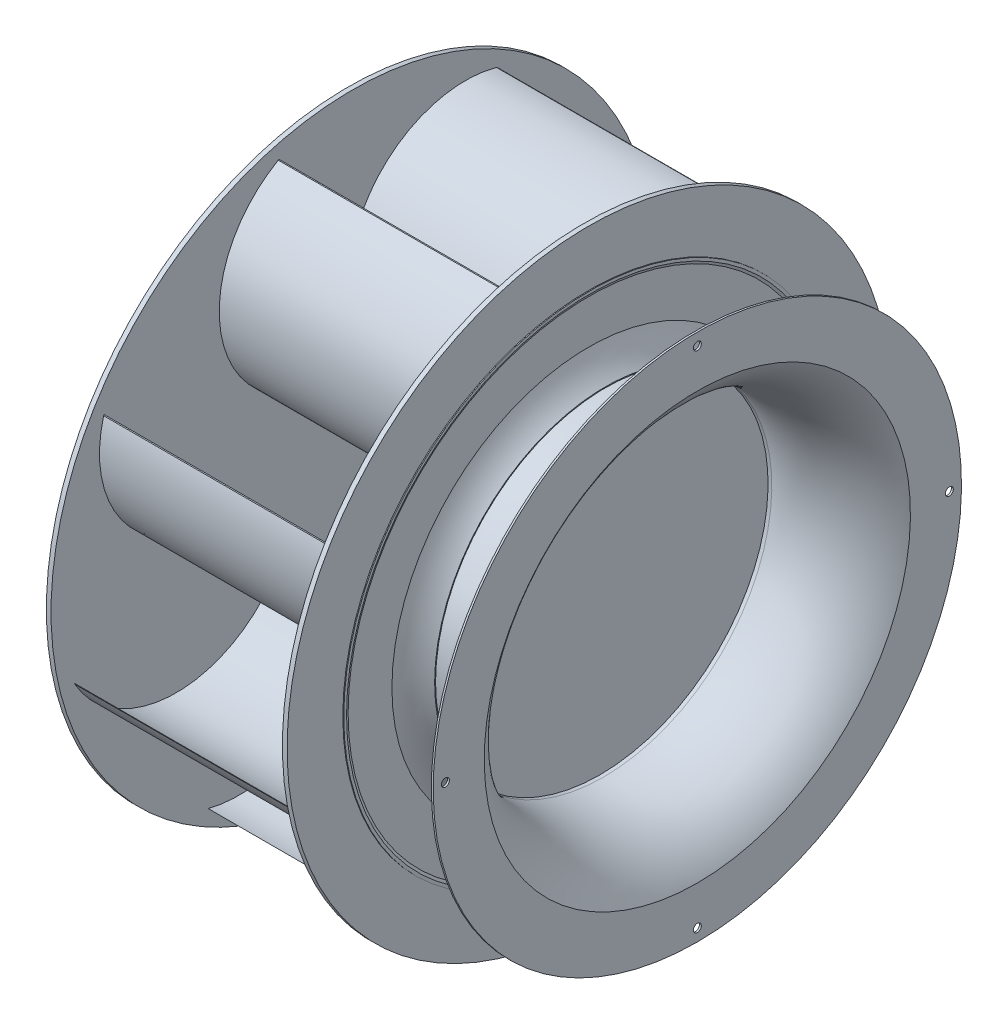
SolidWorks part; units mm, degrees
ref_plane "Front Plane" through (0, 0, 0) normal (0, 0, 1) x (1, 0, 0)
ref_plane "Top Plane" through (0, 0, 0) normal (0, 1, 0) x (1, 0, 0)
ref_plane "Right Plane" through (0, 0, 0) normal (1, 0, 0) x (0, 0, -1)
sketch "Sketch1" plane through (0, 0, 0) normal (0, 0, 1) x (1, 0, 0)
  line L0 (0, 0) -> (831.9083, 0) construction
  line L1 (0, 0) -> (0, 109)
  line L2 (5, 114) -> (70, 114)
  line L3 (70, 114) -> (70, 138)
  line L4 (70, 138) -> (90, 138)
  line L5 (90, 138) -> (90, 98)
  line L6 (90, 98) -> (95, 98)
  line L7 (95, 98) -> (95, 133)
  line L8 (95, 133) -> (105, 133)
  line L9 (105, 133) -> (105, 98)
  line L10 (105, 98) -> (129, 98)
  line L11 (129, 98) -> (129, 0)
  line L12 (129, 0) -> (0, 0)
  arc A0 (5, 114) -> (0, 109) centre (5, 109) ccw
  point P16 (0, 114)
  dimension "D10" = 5
  dimension "D1" = 114
  dimension "D2" = 24
  dimension "D3" = 70
  dimension "D4" = 40
  dimension "D5" = 35
  dimension "D6" = 5
  dimension "D7" = 20
  dimension "D8" = 10
  dimension "D9" = 59
revolve "Revolve1" add sketch "Sketch1" angle 360 about L0
sketch "Sketch2" plane through (129, 0, 0) normal (1, 0, 0) x (0, 0, -1)
  circle A0 centre (0, 0) radius 322
  dimension "D1" = 644
extrude "Extrude1" add sketch "Sketch2" along normal blind 5
sketch "Sketch9" plane through (129, 0, 0) normal (-1, 0, 0) x (0, 0, 1)
  circle A0 centre (0, 0) radius 317
  circle A1 centre (0, 0) radius 100
  circle A2 centre (0, 0) radius 322 construction
  dimension "D1" = 5
  dimension "D2" = 200
extrude "Extrude7" cut sketch "Sketch9" against normal blind 3
ref_plane "Plane1" through (381, 0, 0) normal (1, 0, 0) x (0, 0, -1)
sketch "Sketch3" plane through (381, 0, 0) normal (1, 0, 0) x (0, 0, -1)
  circle A0 centre (0, 0) radius 322
  dimension "D1" = 644
extrude "Extrude2" add sketch "Sketch3" along normal blind 5 separate body
sketch "Sketch4" plane through (134, 0, 0) normal (1, 0, 0) x (0, 0, -1)
  line L0 (0, 0) -> (0, 307) construction
  line L1 (0, 0) -> (161, 278.8602) construction
  line L2 (0, 112.5) -> (0.866, 112)
  line L3 (153.5, 265.8698) -> (154.366, 265.3698)
  circle A0 centre (0, 0) radius 307 construction
  circle A1 centre (0, 0) radius 322 construction
  circle A2 centre (0, 0) radius 112.5 construction
  arc A3 (0, 112.5) -> (153.5, 265.8698) centre (120.6282, 145.2694) cw
  arc A4 (0.866, 112) -> (154.366, 265.3698) centre (121.4942, 144.7694) cw
  dimension "D1" = 15
  dimension "D2" = 225
  dimension "D6" = 125
  dimension "D7" = 125
  dimension "D3" = 30
  dimension "D4" = 60
  dimension "D5" = 1
extrude "Extrude3" add sketch "Sketch4" along normal up to surface (252 mm away) up to face at (386, 0, -322)
ref_axis "Axis1" through (253.5503, 0, 0) along (-1, 0, 0)
pattern_circular "CirPattern1" count 8 over 360 about axis through (253.5503, 0, 0) along (-1, 0, 0) of "Extrude3"
sketch "Sketch5" plane through (0, 0, 0) normal (0, 0, 1) x (1, 0, 0)
  line L0 (0, 0) -> (527.2916, 0) construction
  line L1 (253.5503, 0) -> (75.411, 0) construction
  line L2 (386, 262.5) -> (387, 262.5)
  line L3 (387, 262.5) -> (387, 259.5)
  line L4 (386, 262.5) -> (386, 259.5)
  line L5 (404, 182.5) -> (404, 181.5)
  line L6 (70, 138) -> (70, -138) construction
  line L7 (386, -322) -> (386, 322) construction
  arc A0 (387, 259.5) -> (404, 182.5) centre (451.9802, 233.4696) ccw
  arc A1 (386, 259.5) -> (404, 181.5) centre (450.9575, 233.4133) ccw
  dimension "D7" = 70
  dimension "D8" = 70
  dimension "D1" = 181.5
  dimension "D2" = 1
  dimension "D3" = 1
  dimension "D4" = 3
  dimension "D5" = 262.5
  dimension "D6" = 334
revolve "Revolve2" add sketch "Sketch5" angle 360 about L0
ref_plane "Plane3" through (502, 0, 0) normal (1, 0, 0) x (0, 0, -1)
sketch "Sketch6" plane through (0, 0, 0) normal (0, 0, 1) x (1, 0, 0)
  line L0 (502, 282) -> (500, 282)
  line L1 (502, -251.35) -> (502, 251.35) construction
  line L2 (500, 282) -> (500, 227.5)
  line L3 (0, 0) -> (615.1417, 0) construction
  line L4 (0, 114) -> (0, -114) construction
  line L5 (253.5503, 0) -> (75.411, 0) construction
  line L6 (502, 282) -> (502, 227.5)
  line L7 (398, 181.5) -> (402, 181.5)
  line L8 (398, 181.5) -> (398, 179.5)
  line L9 (398, 179.5) -> (402, 179.5)
  arc A0 (402, 181.5) -> (500, 227.5) centre (415.2724, 280.6153) ccw
  arc A1 (402, 179.5) -> (502, 227.5) centre (415.9922, 278.5163) ccw
  dimension "D7" = 100
  dimension "D8" = 100
  dimension "D1" = 282
  dimension "D2" = 2
  dimension "D3" = 227.5
  dimension "D4" = 104
  dimension "D5" = 181.5
  dimension "D6" = 4
revolve "Revolve3" add sketch "Sketch6" angle 360 about L3
sketch "Sketch7" plane through (502, 0, 0) normal (1, 0, 0) x (0, 0, -1)
  line L0 (0, 0) -> (0, 269) construction
  circle A0 centre (0, 0) radius 269 construction
  circle A1 centre (0, 269) radius 4.25
  dimension "D1" = 538
  dimension "D2" = 8.5
extrude "Extrude5" cut sketch "Sketch7" against normal blind 5
pattern_circular "CirPattern2" count 4 over 360 about axis through (253.5503, 0, 0) along (-1, 0, 0) of "Extrude5"
sketch "Sketch8" plane through (0, 0, 0) normal (1, 0, 0) x (0, 0, -1)
  line L0 (0, 0) -> (0, 126) construction
  circle A0 centre (0, 0) radius 126 construction
  circle A1 centre (0, 126) radius 5
  dimension "D1" = 252
  dimension "D2" = 10
extrude "Extrude6" cut sketch "Sketch8" along normal up to surface (90 mm away) up to face at (90, 0, 138)
pattern_circular "CirPattern3" count 8 over 360 about axis through (253.5503, 0, 0) along (-1, 0, 0) of "Extrude6"
